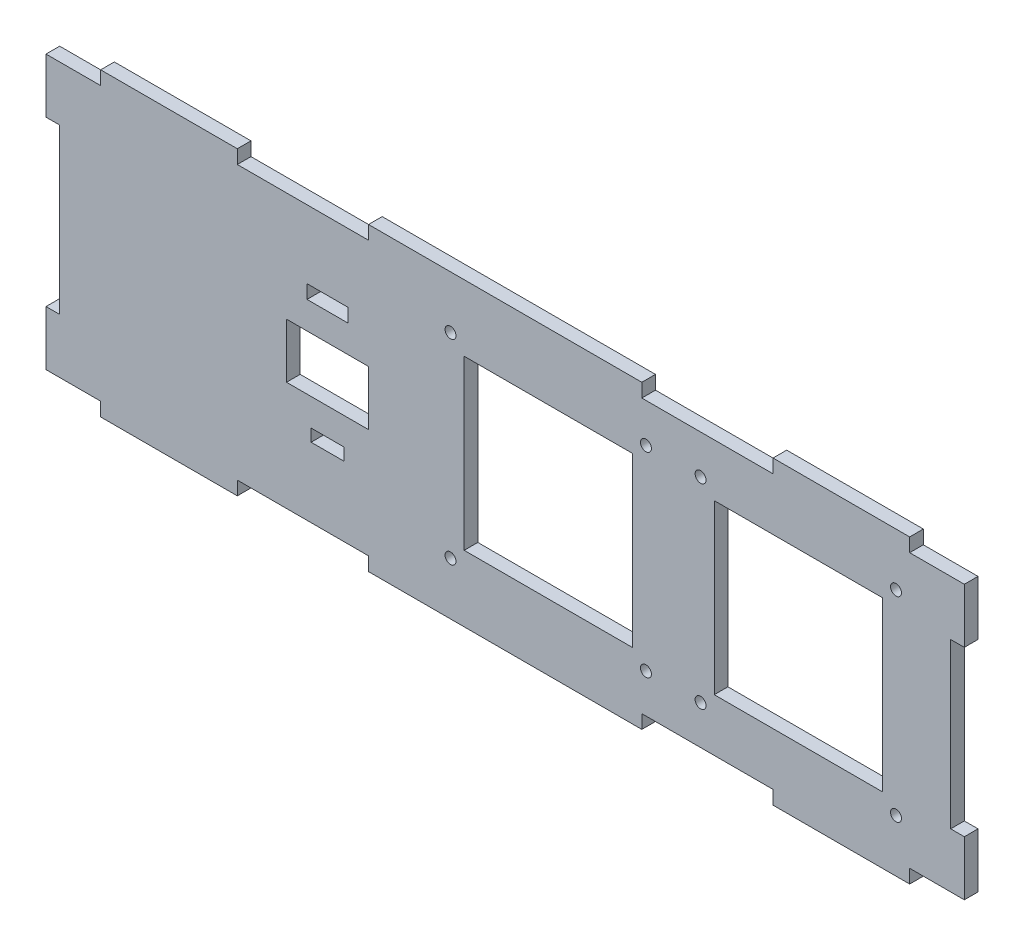
SolidWorks part; units mm, degrees
ref_plane "Front Plane" through (0, 0, 0) normal (0, 0, 1) x (1, 0, 0)
ref_plane "Top Plane" through (0, 0, 0) normal (0, 1, 0) x (1, 0, 0)
ref_plane "Right Plane" through (0, 0, 0) normal (1, 0, 0) x (0, 0, -1)
sketch "Sketch1" plane through (0, 0, 0) normal (0, 0, 1) x (1, 0, 0)
  line L0 (-168, 0) -> (168, 0) construction
  line L1 (168, -50) -> (-168, -50)
  line L2 (168, -50) -> (168, 50)
  line L3 (168, 50) -> (-168, 50)
  line L4 (-168, -50) -> (-168, 50)
  line L5 (168, -50) -> (-168, 50) construction
  line L6 (168, 50) -> (-168, -50) construction
  line L7 (0, 50) -> (0, -50) construction
  line L8 (-168, 30) -> (-163, 30)
  line L9 (-148, 50) -> (-98, 50)
  line L10 (-148, 50) -> (-148, 55)
  line L11 (-148, 55) -> (-98, 55)
  line L12 (-98, 50) -> (-98, 55)
  line L13 (0, 50) -> (-50, 50)
  line L15 (50, 55) -> (-50, 55)
  line L16 (-50, 50) -> (-50, 55)
  line L17 (-163, 30) -> (-163, -30)
  line L18 (-50, -50) -> (-50, -55)
  line L19 (50, -55) -> (-50, -55)
  line L20 (-168, -30) -> (-163, -30)
  line L21 (-148, -50) -> (-148, -55)
  line L22 (-98, -50) -> (-98, -55)
  line L23 (-148, -55) -> (-98, -55)
  line L24 (50, 50) -> (50, 55)
  line L25 (148, 50) -> (148, 55)
  line L26 (98, 50) -> (98, 55)
  line L27 (148, 55) -> (98, 55)
  line L28 (50, -50) -> (50, -55)
  line L29 (98, -50) -> (98, -55)
  line L30 (148, -50) -> (148, -55)
  line L31 (148, -55) -> (98, -55)
  line L32 (168, -30) -> (163, -30)
  line L33 (168, 30) -> (163, 30)
  line L34 (163, 30) -> (163, -30)
  line L35 (-50, 50) -> (50, 50)
  line L36 (-148, 50) -> (-98, 50)
  line L37 (98, 50) -> (148, 50)
  line L38 (168, 30) -> (168, -30)
  line L39 (148, -50) -> (98, -50)
  line L40 (50, -50) -> (-50, -50)
  line L41 (-98, -50) -> (-148, -50)
  line L42 (-168, 30) -> (-168, -30)
  line L54 (-20, 35.75) -> (51.5, -35.75) construction
  line L55 (-20, -35.75) -> (51.5, 35.75) construction
  line L56 (71.5, 35.75) -> (143, -35.75) construction
  line L57 (71.5, -35.75) -> (143, 35.75) construction
  line L58 (-65, 10) -> (-65, 35.75) construction
  line L59 (46.5, -30.75) -> (-15, -30.75)
  line L60 (46.5, -30.75) -> (46.5, 30.75)
  line L61 (46.5, 30.75) -> (-15, 30.75)
  line L62 (-15, -30.75) -> (-15, 30.75)
  line L63 (46.5, -30.75) -> (-15, 30.75) construction
  line L64 (46.5, 30.75) -> (-15, -30.75) construction
  line L65 (138, -30.75) -> (76.5, -30.75)
  line L66 (138, -30.75) -> (138, 30.75)
  line L67 (138, 30.75) -> (76.5, 30.75)
  line L68 (76.5, -30.75) -> (76.5, 30.75)
  line L69 (138, -30.75) -> (76.5, 30.75) construction
  line L70 (138, 30.75) -> (76.5, -30.75) construction
  line L71 (-80, -10) -> (-50, -10)
  line L72 (-80, -10) -> (-80, 10)
  line L73 (-80, 10) -> (-50, 10)
  line L74 (-50, -10) -> (-50, 10)
  line L75 (-80, -10) -> (-50, 10) construction
  line L76 (-80, 10) -> (-50, -10) construction
  line L77 (-72.5, 25) -> (-57.5, 25)
  line L81 (-72.5, 20) -> (-72.5, 25)
  line L82 (-72.5, 20) -> (-57.5, 20)
  line L83 (-65, 10) -> (-65, -50) construction
  line L84 (-65, 35.75) -> (-65, 50) construction
  line L85 (-59, -20) -> (-71, -20)
  line L86 (-71, -20) -> (-71, -24.5)
  line L87 (-71, -24.5) -> (-59, -24.5)
  line L88 (-59, -20) -> (-59, -24.5)
  line L89 (-57.5, 20) -> (-57.5, 25)
  circle A0 centre (-20, 35.75) radius 2
  circle A1 centre (51.5, 35.75) radius 2
  circle A2 centre (-20, -35.75) radius 2
  circle A3 centre (51.5, -35.75) radius 2
  circle A4 centre (71.5, 35.75) radius 2
  circle A5 centre (143, 35.75) radius 2
  circle A6 centre (71.5, -35.75) radius 2
  circle A7 centre (143, -35.75) radius 2
  point P0 (0, 0)
  point P24 (-163, 0)
  point P31 (0, 55)
  point P37 (0, -55)
  point P61 (15.75, 0)
  point P66 (107.25, 0)
  point P75 (-65, 0)
  point P86 (-65, 25)
  point P93 (-65, -24.5)
  point P94 (-65, -20)
  point P96 (-65, 20)
  dimension "D17" = 61.5
  dimension "D1" = 100
  dimension "D2" = 336
  dimension "D3" = 5
  dimension "D4" = 5
  dimension "D5" = 50
  dimension "D6" = 50
  dimension "D7" = 5
  dimension "D8" = 30
  dimension "D9" = 20
  dimension "D10" = 20
  dimension "D12" = 71.5
  dimension "D13" = 71.5
  dimension "D15" = 71.5
  dimension "D16" = 71.5
  dimension "D20" = 20
  dimension "D21" = 30
  dimension "D22" = 5
  dimension "D23" = 7.5
  dimension "D24" = 10
  dimension "D25" = 6
  dimension "D26" = 4.5
  dimension "D27" = 10
extrude "Boss-Extrude1" add sketch "Sketch1" along normal blind 5 contours L34 L33 L2 L3 L4 L8 L17 L20 L1 L32 | L28 L1 L18 L19 | L31 L30 L1 L29 | L25 L27 L26 L3 | L3 L12 L11 L10 | L23 L22 L41 L21 | L35 L24 L15 L16 region at (-17.2322, -0.0198, 0) region at (123, -52.5, 0) region at (0, -52.5, 0) region at (123, 52.5, 0) region at (-123, 52.5, 0)
